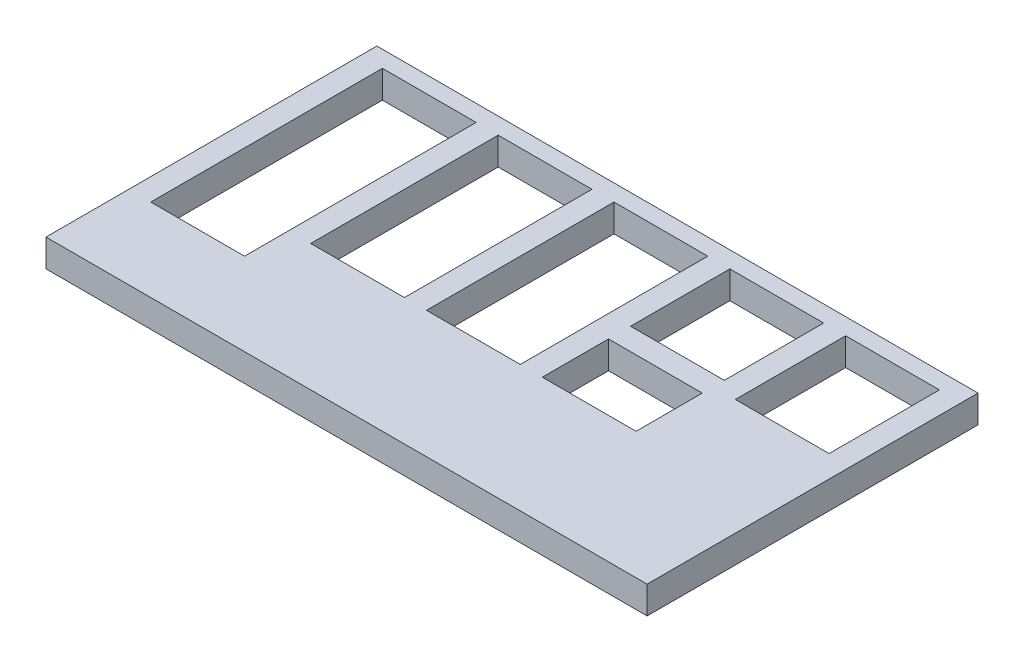
SolidWorks part; units mm, degrees
ref_plane "Front" through (0, 0, 0) normal (0, 0, 1) x (1, 0, 0)
ref_plane "Top" through (0, 0, 0) normal (0, 1, 0) x (1, 0, 0)
ref_plane "Right" through (0, 0, 0) normal (1, 0, 0) x (0, 0, -1)
sketch "Sketch1" plane through (0, 0, 0) normal (0, 1, 0) x (1, 0, 0)
  line L1 (-54.5, -30) -> (54.5, -30)
  line L2 (-54.5, -30) -> (-54.5, 30)
  line L3 (-54.5, 30) -> (54.5, 30)
  line L4 (54.5, -30) -> (54.5, 30)
  line L5 (-54.5, -30) -> (54.5, 30) construction
  line L6 (-54.5, 30) -> (54.5, -30) construction
  line L12 (12.5, 9) -> (29.5, 9)
  line L13 (-50.5, -15) -> (-33.5, -15)
  line L14 (-50.5, -15) -> (-50.5, 27)
  line L15 (-50.5, 27) -> (-33.5, 27)
  line L16 (-33.5, -15) -> (-33.5, 27)
  line L17 (-50.5, -15) -> (-33.5, 27) construction
  line L18 (-50.5, 27) -> (-33.5, -15) construction
  line L23 (12.5, 9) -> (12.5, 27)
  line L24 (12.5, 27) -> (29.5, 27)
  line L25 (-12.5, 27) -> (-29.5, 27)
  line L26 (-12.5, 27) -> (-12.5, -7)
  line L27 (-12.5, -7) -> (-29.5, -7)
  line L28 (-29.5, 27) -> (-29.5, -7)
  line L29 (-12.5, 27) -> (-29.5, -7) construction
  line L30 (-12.5, -7) -> (-29.5, 27) construction
  line L35 (29.5, 9) -> (29.5, 27)
  line L36 (12.5, 9) -> (29.5, 27) construction
  line L37 (-8.5, -7) -> (8.5, -7)
  line L38 (-8.5, -7) -> (-8.5, 27)
  line L39 (-8.5, 27) -> (8.5, 27)
  line L40 (8.5, -7) -> (8.5, 27)
  line L41 (-8.5, -7) -> (8.5, 27) construction
  line L42 (-8.5, 27) -> (8.5, -7) construction
  line L48 (12.5, 27) -> (29.5, 9) construction
  line L49 (33.5, 7) -> (50.5, 7)
  line L50 (33.5, 7) -> (33.5, 27)
  line L51 (33.5, 27) -> (50.5, 27)
  line L52 (50.5, 7) -> (50.5, 27)
  line L53 (33.5, 7) -> (50.5, 27) construction
  line L54 (33.5, 27) -> (50.5, 7) construction
  line L55 (12.5, 5) -> (29.5, 5)
  line L56 (12.5, 5) -> (12.5, -7)
  line L57 (12.5, -7) -> (29.5, -7)
  line L58 (29.5, 5) -> (29.5, -7)
  line L59 (12.5, 5) -> (29.5, -7) construction
  line L60 (12.5, -7) -> (29.5, 5) construction
  line L67 (-54.5, -30) -> (54.5, -30)
  point P0 (0, 0)
  point P6 (42, 17)
  point P9 (21, 18)
  point P11 (-42, 6)
  point P21 (-21, 10)
  point P26 (21, -1)
  point P31 (0, 10)
  point P36 (0, 0)
  point P37 (29.5, -30)
  point P39 (32.5038, -30)
  point P40 (0, 0)
  point P41 (55.4601, -30)
  point P42 (0, 0)
  point P43 (-71.4536, -30)
  point P44 (63.1175, -30)
  point P45 (-55.4299, -30)
  dimension "D1" = 109
  dimension "D2" = 60
  dimension "D3" = 4
  dimension "D4" = 3
  dimension "D5" = 17
  dimension "D6" = 4
  dimension "D7" = 17
  dimension "D8" = 3
  dimension "D9" = 4
  dimension "D10" = 3
  dimension "D11" = 17
  dimension "D12" = 4
  dimension "D13" = 17
  dimension "D14" = 18
  dimension "D15" = 4
  dimension "D16" = 17
  dimension "D17" = 20
  dimension "D18" = 12
  dimension "D19" = 4
  dimension "D21" = 42
  dimension "D22" = 34
  dimension "D23" = 4
  dimension "D25" = 34
extrude "Boss-Extrude1" add sketch "Sketch1" along normal blind 5 contours L1 L4 L3 L2 L52 L49 L50 L51 L40 L37 L38 L39 L35 L12 L23 L24 L28 L25 L26 L27 L16 L13 L14 L15 L55 L58 L57 L56 region at (4.4859, 0, 7.0492)
